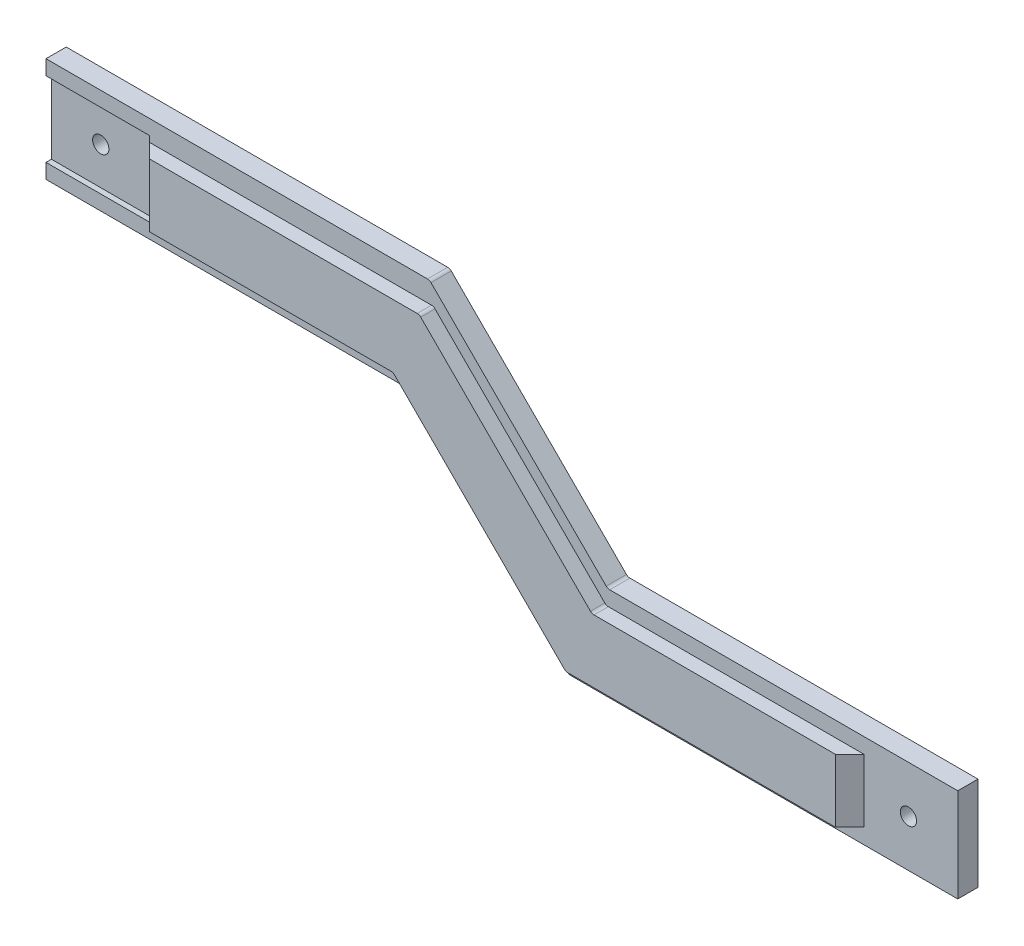
SolidWorks part; units mm, degrees
ref_plane "前视基准面" through (0, 0, 0) normal (0, 0, 1) x (1, 0, 0)
ref_plane "上视基准面" through (0, 0, 0) normal (0, 1, 0) x (1, 0, 0)
ref_plane "右视基准面" through (0, 0, 0) normal (1, 0, 0) x (0, 0, -1)
sketch "草图1" plane through (0, 0, 0) normal (0, 0, 1) x (1, 0, 0)
  line L0 (-92.4, 27) -> (-13.565, 27)
  line L1 (-13.565, 27) -> (21.435, -8)
  line L2 (21.435, -8) -> (92.4, -8)
  line L3 (92.4, -8) -> (92.4, -27)
  line L4 (92.4, -27) -> (13.565, -27)
  line L5 (13.565, -27) -> (-21.435, 8)
  line L6 (-21.435, 8) -> (-92.4, 8)
  line L7 (-92.4, 8) -> (-92.4, 27)
  line L8 (-13.565, 27) -> (13.565, -27) construction
  line L9 (-21.435, 8) -> (21.435, -8) construction
  circle A0 centre (-82.4, 17.5) radius 1.65
  circle A1 centre (82.4, -17.5) radius 1.65
  dimension "D2" = 3.3
  dimension "D1" = 19
  dimension "D3" = 164.8
  dimension "D4" = 35
  dimension "D5" = 9.5
  dimension "D6" = 9.5
  dimension "D7" = 135
  dimension "D8" = 19
  dimension "D9" = 10
  dimension "D10" = 10
extrude "凸台-拉伸1" add sketch "草图1" along normal blind 3
sketch "草图2" plane through (0, 0, 3) normal (0, 0, 1) x (1, 0, 0)
  line L0 (-71.4, 23.9) -> (-71.4, 11.1)
  line L1 (-71.4, 11.1) -> (-19.151, 11.1)
  line L2 (-19.151, 11.1) -> (15.849, -23.9)
  line L3 (15.849, -23.9) -> (73.4, -23.9)
  line L4 (73.4, -23.9) -> (73.4, -11.1)
  line L5 (73.4, -11.1) -> (21.151, -11.1)
  line L6 (21.151, -11.1) -> (-13.849, 23.9)
  line L7 (-13.849, 23.9) -> (-71.4, 23.9)
  line L8 (-13.565, 27) -> (-92.4, 27) construction
  line L9 (13.565, -27) -> (92.4, -27) construction
  line L10 (92.4, -27) -> (92.4, -8) construction
  line L11 (-92.4, 27) -> (-92.4, 8) construction
  line L12 (21.435, -8) -> (-13.565, 27) construction
  dimension "D1" = 12.8
  dimension "D2" = 12.8
  dimension "D3" = 3.1
  dimension "D4" = 3.1
  dimension "D5" = 19
  dimension "D6" = 21
  dimension "D7" = 12.8
extrude "凸台-拉伸2" add sketch "草图2" along normal blind 2.9
chamfer "倒角1" distance 2.9 angle 45 2 edges at (73.4, -17.5, 5.9) (-71.4, 17.5, 5.9)
sketch "草图6" plane through (0, 0, 0) normal (0, 0, 1) x (1, 0, 0)
  line L0 (-92.4, 28.1) -> (-92.4, 6.9)
  line L1 (-92.4, 6.9) -> (-20.335, 6.9)
  line L2 (-21.435, 8) -> (13.565, -27) construction
  line L3 (-20.335, 6.9) -> (13.565, -27)
  line L4 (13.565, -27) -> (92.4, -27)
  line L5 (92.4, -27) -> (92.4, -8)
  line L6 (92.4, -8) -> (21.435, -8)
  line L7 (21.435, -8) -> (-14.665, 28.1)
  line L8 (-14.665, 28.1) -> (-92.4, 28.1)
  line L9 (-92.4, 27) -> (-92.4, 8) construction
  line L10 (-92.4, 8) -> (-21.435, 8) construction
  circle A0 centre (-82.4, 17.5) radius 1.65
  circle A1 centre (82.4, -17.5) radius 1.65
  dimension "D3" = 3.3
  dimension "D1" = 21.2
  dimension "D2" = 1.1
extrude "凸台-拉伸3" add sketch "草图6" against normal blind 4.1 from offset 3
sketch "草图7" plane through (0, 0, 0) normal (0, 0, 1) x (1, 0, 0)
  line L0 (-92.4, 25.1) -> (-92.4, 9.9)
  line L1 (-92.4, 9.9) -> (-71.4, 9.9)
  line L3 (-71.4, 9.9) -> (-71.4, 25.1)
  line L5 (-71.4, 25.1) -> (-92.4, 25.1)
  line L6 (-14.665, 28.1) -> (-92.4, 28.1) construction
  line L7 (-92.4, 6.9) -> (-20.335, 6.9) construction
  line L8 (-92.4, 28.1) -> (-92.4, 6.9) construction
  dimension "D1" = 21
  dimension "D2" = 3
  dimension "D3" = 3
extrude "切除-拉伸1" cut sketch "草图7" against normal blind 1.1 from offset 3
fillet "圆角1" radius 1 8 edges at (-13.849, 23.9, 4.45) (-14.665, 28.1, 0.95) (21.435, -8, 0.95) (21.151, -11.1, 4.45) (13.565, -27, 0.95) (15.849, -23.9, 4.45) (-19.151, 11.1, 4.45) (-20.335, 6.9, 0.95)
